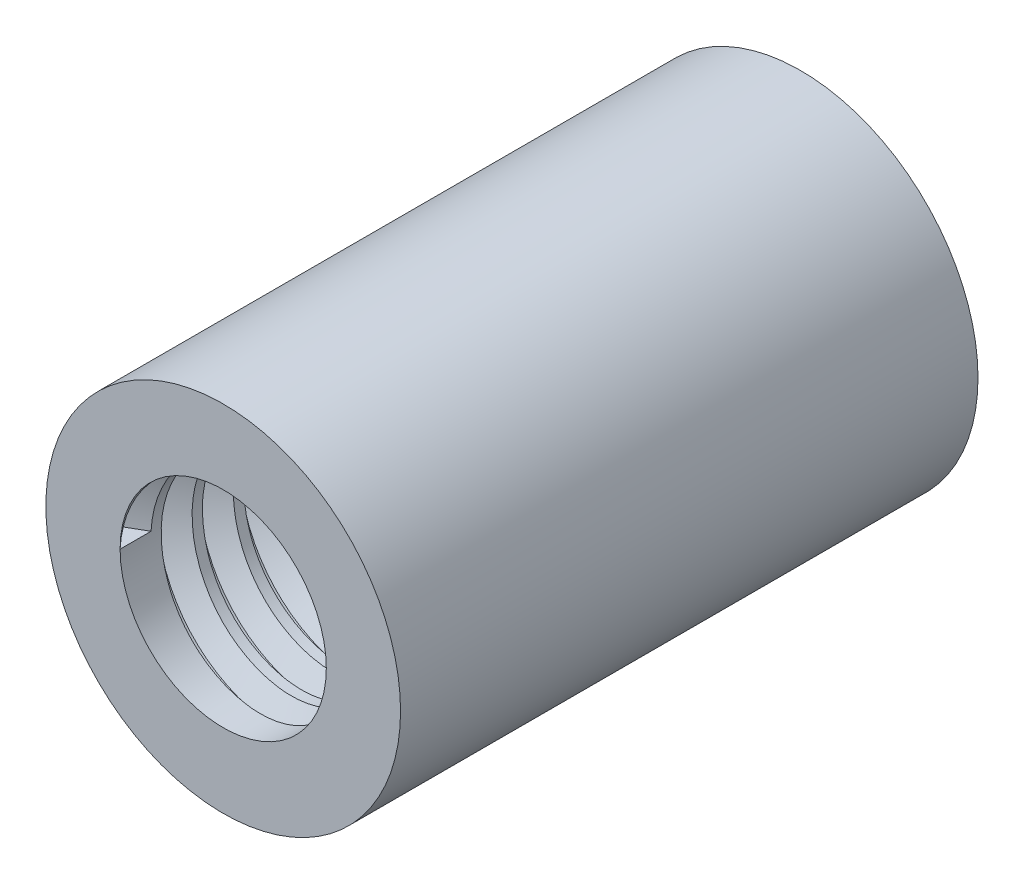
SolidWorks part; units mm, degrees
ref_plane "Ön Düzlem" through (0, 0, 0) normal (0, 0, 1) x (1, 0, 0)
ref_plane "Üst Düzlem" through (0, 0, 0) normal (0, 1, 0) x (1, 0, 0)
ref_plane "Sağ Düzlem" through (0, 0, 0) normal (1, 0, 0) x (0, 0, -1)
sketch "Çizim1" plane through (0, 0, 0) normal (0, 0, 1) x (1, 0, 0)
  circle A0 centre (0, 0) radius 2.15
  circle A1 centre (0, 0) radius 1.25
  dimension "D1" = 4.3
  dimension "D2" = 2.5
extrude "Yükseklik-Ekstrüzyon1" add sketch "Çizim1" along normal blind 7
thread "Diş1" pitch 0.5 method cut profile "Diş Profili1" start angle 0, offset 0, length 0, pitch 0.5, diameter 2.5
ref_plane "Düzlem1" through (-1.25, 0, 7) normal (0, -1, 0) x (-1, 0, 0)
sketch "Diş Profili1" plane through (-1.25, 0, 7) normal (0, -1, 0) x (-1, 0, 0)
  line L0 (0, 0) -> (0, 0.5) construction
  line L1 (0, 0) -> (0.2706, 0.1562)
  line L2 (0.2706, 0.1562) -> (0.2706, 0.2187)
  line L3 (0.2706, 0.2187) -> (0, 0.375)
  line L4 (0.2706, 0.1875) -> (0, 0.1875) construction
  line L11 (0, 0) -> (0, 0.375)
  point P2 (0, 0)
  dimension "Pitch" = 0.5
  dimension "Profile_Angle" = 60
  dimension "Profile_Land" = 0.0625
  dimension "Profile_Height" = 0.2706
